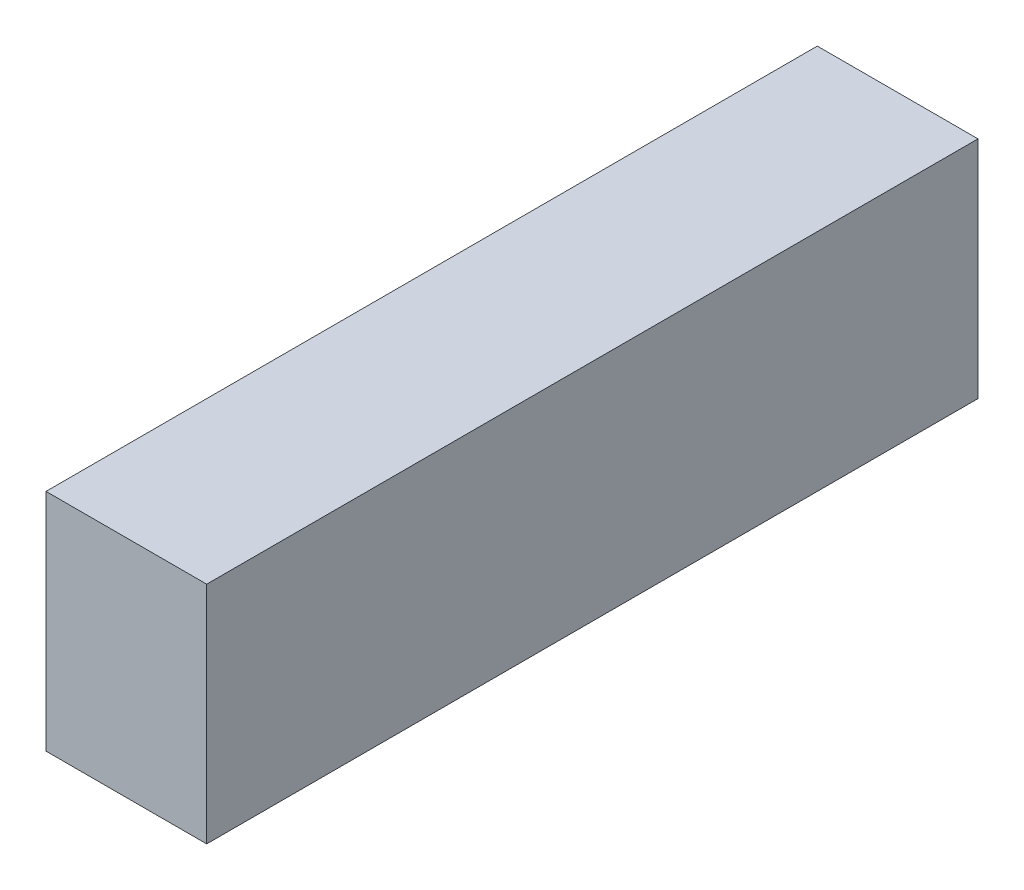
SolidWorks part; units mm, degrees
material "Silicon Rubber"
ref_plane "Front Plane" through (0, 0, 0) normal (0, 0, 1) x (1, 0, 0)
ref_plane "Top Plane" through (0, 0, 0) normal (0, 1, 0) x (1, 0, 0)
ref_plane "Right Plane" through (0, 0, 0) normal (1, 0, 0) x (0, 0, -1)
sketch "Sketch1" plane through (0, 0, 0) normal (1, 0, 0) x (0, 0, -1)
  line L1 (-60, -17.5) -> (60, -17.5)
  line L2 (-60, -17.5) -> (-60, 17.5)
  line L3 (-60, 17.5) -> (60, 17.5)
  line L4 (60, -17.5) -> (60, 17.5)
  line L5 (-60, -17.5) -> (60, 17.5) construction
  line L6 (-60, 17.5) -> (60, -17.5) construction
  point P0 (0, 0)
  dimension "D1" = 120
  dimension "D2" = 35
extrude "Boss-Extrude1" add sketch "Sketch1" along normal blind 25
